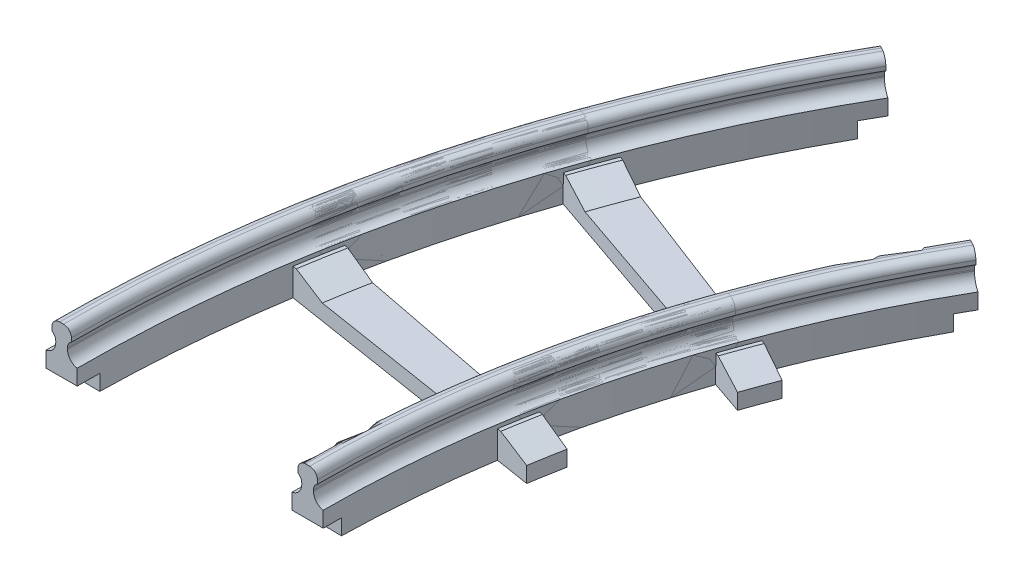
SolidWorks part; units mm, degrees
other "标注1"
sketch "草图3" plane through (-22.25, 4, -10) normal (-0.231, 0.6469, -0.7268) x (-0.9696, -0.2151, 0.1167)
ref_plane "前视基准面" through (0, 0, 0) normal (0, 0, 1) x (1, 0, 0)
ref_plane "上视基准面" through (0, 0, 0) normal (0, 1, 0) x (1, 0, 0)
ref_plane "右视基准面" through (0, 0, 0) normal (1, 0, 0) x (0, 0, -1)
other "Configuration Table"
sketch "草图4" plane through (0, 0, 0) normal (0, 0, 1) x (1, 0, 0)
  line L0 (0, 0) -> (31.5, 0) construction
  line L1 (0.75, -1.5) -> (1.25, -1.5)
  line L3 (0, 0) -> (1.25, 0)
  line L4 (1.25, -1.5) -> (1.25, 0)
  line L5 (0, 0) -> (-1.25, 0)
  line L10 (0.75, -1.5) -> (0.75, -4)
  line L11 (-0.75, -1.5) -> (-1.25, -1.5)
  line L12 (0.75, -4) -> (2, -4)
  line L14 (0, -8) -> (2, -8)
  line L15 (2, -4) -> (2, -8)
  line L16 (-1.25, 0) -> (-1.25, -1.5)
  line L20 (-0.75, -1.5) -> (-0.75, -4)
  line L21 (-0.75, -4) -> (-2, -4)
  line L23 (0, -8) -> (-2, -8)
  line L24 (-2, -4) -> (-2, -8)
  line L25 (31.5, 0) -> (32.75, 0)
  line L26 (30.25, 0) -> (31.5, 0)
  line L27 (30.25, 0) -> (30.25, -1.5)
  line L28 (30.25, -1.5) -> (30.75, -1.5)
  line L31 (30.75, -1.5) -> (30.75, -4)
  line L34 (29.5, -4) -> (30.75, -4)
  line L35 (29.5, -4) -> (29.5, -8)
  line L36 (29.5, -8) -> (31.5, -8)
  line L39 (32.25, -1.5) -> (32.75, -1.5)
  line L40 (32.75, 0) -> (32.75, -1.5)
  line L42 (32.25, -1.5) -> (32.25, -4)
  line L45 (32.25, -4) -> (33.5, -4)
  line L47 (31.5, -8) -> (33.5, -8)
  line L48 (33.5, -4) -> (33.5, -8)
  point P0 (0, 0)
  point P2 (15.75, 0)
  dimension "D1" = 1.25
  dimension "D4" = 2.5
sketch "草图6" plane through (0, 0, 0) normal (0, 0, 1) x (1, 0, 0)
  line L0 (165.75, 3.8535) -> (165.75, -12.2756)
  dimension "D1" = 150
revolve "旋转1" add sketch "草图4" angle 10 about L0
fillet "圆角1" radius 1.5 2 edges at (1.3779, -4, -14.3807) (-0.1164, -4, -14.5114)
fillet "圆角2" radius 1.5 2 edges at (31.2637, -4, -11.766) (32.758, -4, -11.6353)
fillet "圆角3" radius 1 4 edges at (33.2561, 0, -11.5917) (30.7656, 0, -11.8096) (31.2637, -1.5, -11.766) (32.758, -1.5, -11.6353)
fillet "圆角4" radius 1 4 edges at (1.876, 0, -14.3371) (-0.1164, -1.5, -14.5114) (1.3779, -1.5, -14.3807) (-0.6145, 0, -14.555)
sketch "草图7" plane through (0, 0, 0) normal (0, 0, 1) x (1, 0, 0)
  line L1 (-2, -8) -> (2, -8)
  line L2 (-2, -8) -> (-2, -6)
  line L3 (-2, -6) -> (2, -6)
  line L4 (2, -8) -> (2, -6)
  line L5 (33.5, -8) -> (33.5, -4) construction
  line L6 (29.5, -8) -> (33.5, -8)
  line L7 (29.5, -8) -> (29.5, -6)
  line L8 (29.5, -6) -> (33.5, -6)
  line L9 (33.5, -8) -> (33.5, -6)
  line L10 (2, -8) -> (2, -4) construction
  dimension "D1" = 2
sketch "草图9" plane through (0, 0, 0) normal (0, 1, 0) x (1, 0, 0)
  line L0 (29.5, 0) -> (2, 0)
  line L1 (-2, 0) -> (2, 0) construction
  line L2 (4.4877, 28.4349) -> (31.5699, 23.6596)
  line L3 (18.0288, 26.0472) -> (15.75, 0)
  arc A0 (4.4877, 28.4349) -> (2, 0) centre (165.75, 0) ccw construction
  arc A1 (31.5699, 23.6596) -> (29.5, 0) centre (165.75, 0) ccw construction
  point P20 (165.75, 0)
  dimension "D1" = 10
  dimension "D2" = 26.1467
revolve "切除-旋转1" cut sketch "草图7" angle 1 about L0
sketch "草图10" plane through (0, -6, 0) normal (0, -1, 0) x (1, 0, 0)
  line L0 (-1.9936, -1.4639) -> (2.0062, -1.429) construction
  line L2 (2.0062, -1.429) -> (29.5052, -1.189) construction
  line L3 (29.5052, -1.189) -> (33.505, -1.1541) construction
  circle A1 centre (0.0063, -1.4464) radius 0.4
  circle A2 centre (31.5051, -1.1715) radius 0.4
  arc A3 (-2, 0) -> (-1.9745, -2.9276) centre (165.75, 0) ccw construction
  arc A4 (2, 0) -> (2.0249, -2.8578) centre (165.75, 0) ccw construction
  arc A5 (29.5, 0) -> (29.5208, -2.3779) centre (165.75, 0) ccw construction
  arc A6 (33.5, 0) -> (33.5201, -2.3081) centre (165.75, 0) ccw construction
  dimension "D1" = 0.8
extrude "切除-拉伸1" cut sketch "草图10" against normal blind 2
sketch "草图11" plane through (4.998, 0, -28.3449) normal (0.1736, 0, -0.9848) x (-0.9848, 0, -0.1736)
  line L0 (-26.9819, -4.5) -> (-26.4819, -4.5)
  line L1 (-26.9819, -4) -> (-26.9819, -8) construction
  line L2 (-26.4819, -4.5) -> (-22.4819, -6)
  line L3 (-22.4819, -6) -> (-3.9819, -6)
  line L4 (-3.9819, -6) -> (0.0181, -4.5)
  line L5 (0.0181, -4.5) -> (0.5181, -4.5)
  line L6 (0.5181, -8) -> (0.5181, -4) construction
  line L7 (0.5181, -4.5) -> (4.5181, -4.5)
  line L8 (4.5181, -4) -> (4.5181, -8) construction
  line L9 (4.5181, -4.5) -> (5.0181, -4.5)
  line L10 (5.0181, -4.5) -> (9.0181, -6)
  line L11 (9.0181, -6) -> (9.0181, -8)
  line L13 (-35.4819, -8) -> (-35.4819, -6)
  line L14 (-35.4819, -6) -> (-31.4819, -4.5)
  line L15 (-31.4819, -4.5) -> (-30.9819, -4.5)
  line L16 (-30.9819, -8) -> (-30.9819, -4) construction
  line L17 (-30.9819, -4.5) -> (-26.9819, -4.5)
  line L19 (-35.4819, -8) -> (-30.9819, -8)
  line L20 (-30.9819, -8) -> (-26.9819, -8)
  line L21 (-26.9819, -8) -> (0.5181, -8)
  line L22 (0.5181, -8) -> (4.5181, -8)
  line L23 (4.5181, -8) -> (9.0181, -8)
  dimension "D1" = 0.5
  dimension "D2" = 4.5
  dimension "D3" = 3.5
  dimension "D4" = 2
revolve "旋转2" add sketch "草图11" angle 1 about L0
mirror "镜向1"
pattern_circular "阵列(圆周)1" count 2 over 10 about axis through (165.75, 0, 0) along (0, 1, 0) of bodies 229
